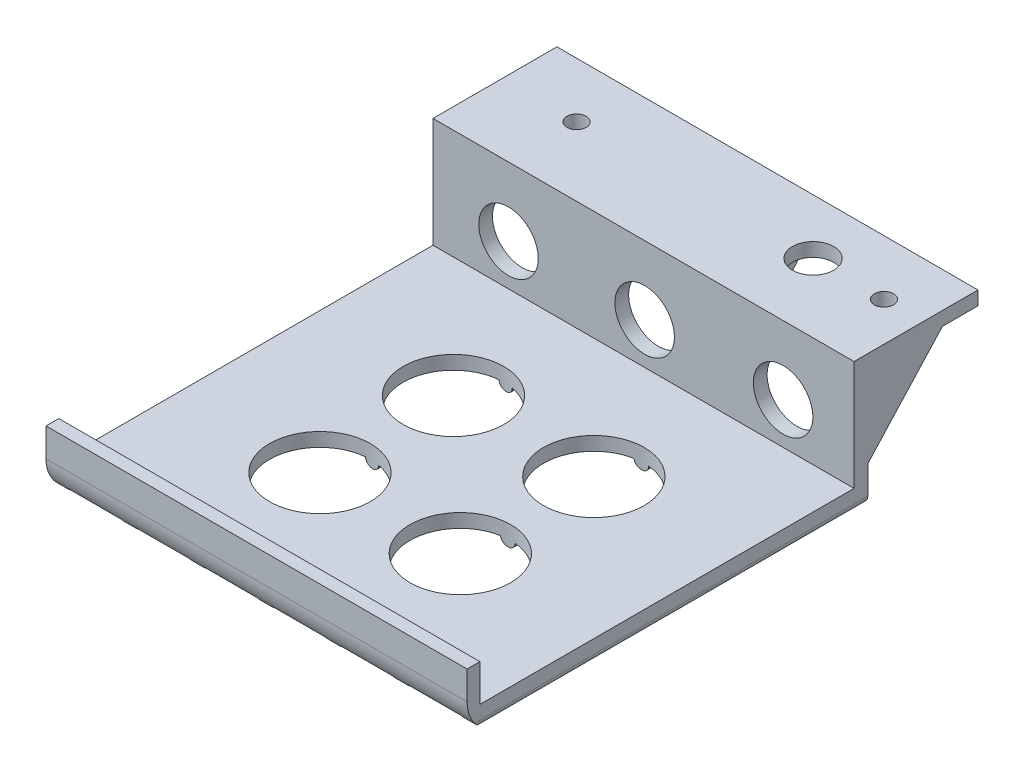
SolidWorks part; units mm, degrees
ref_plane "Plan de face" through (0, 0, 0) normal (0, 0, 1) x (1, 0, 0)
ref_plane "Plan de dessus" through (0, 0, 0) normal (0, 1, 0) x (1, 0, 0)
ref_plane "Plan de droite" through (0, 0, 0) normal (1, 0, 0) x (0, 0, -1)
sketch "Esquisse1" plane through (0, 0, 0) normal (1, 0, 0) x (0, 0, -1)
  line L0 (-109.4897, -87.8002) -> (-136.5699, -87.8002)
  line L1 (-136.5699, -109.8002) -> (-136.5699, -44.8002) construction
  line L2 (-136.5699, -87.8002) -> (-136.5699, -111.8002)
  line L3 (-136.5699, -111.8002) -> (-218.1141, -111.8002)
  line L6 (-109.4897, -90.8002) -> (-133.5699, -90.8002)
  line L7 (-133.5699, -90.8002) -> (-133.5699, -114.8002)
  line L8 (-133.5699, -114.8002) -> (-221.1141, -114.8002)
  line L9 (-221.1141, -114.8002) -> (-221.1141, -103.7104)
  line L10 (-109.4897, -87.8002) -> (-109.4897, -90.8002)
  line L11 (-112.5699, -87.8002) -> (-136.5699, -87.8002) construction
  line L12 (-112.5699, -90.8002) -> (-133.5699, -90.8002) construction
  line L13 (-218.3141, -103.7104) -> (-221.1141, -103.7104)
  line L14 (-218.3141, -103.7104) -> (-218.3141, -111.8002)
  line L15 (-218.1141, -111.8002) -> (-218.3141, -111.8002)
  line L17 (-218.1141, -111.8002) -> (-218.1141, -103.7104) construction
  dimension "D2" = 0.2
  dimension "D1" = 3
extrude "Boss.-Extru.1" add sketch "Esquisse1" against normal blind 92
sketch "Esquisse3" plane through (0, 0, 0) normal (1, 0, 0) x (0, 0, -1)
  line L0 (-117.2572, -90.8002) -> (-133.5699, -108.6357)
  line L1 (-133.5699, -90.8002) -> (-109.4897, -90.8002) construction
  line L2 (-133.5699, -114.8002) -> (-133.5699, -90.8002) construction
rib "Nervure2" sketch "Esquisse3" sketch "Esquisse3" thickness 1 extrusion direction parallel to sketch draft on no parameters "D1"=1
pattern_linear "Répétition linéaire1" count 4 spacing 30 along (-1, 0, 0) of "Nervure2"
sketch "Esquisse4" plane through (0, 0, 133.5699) normal (0, 0, -1) x (-1, 0, 0)
  line L0 (15.5, -90.8002) -> (15.5, -114.8002) construction
  line L1 (30, -90.8002) -> (1, -90.8002) construction
  line L2 (92, -114.8002) -> (0, -114.8002) construction
  line L3 (15.5, -114.8002) -> (46, -114.8002) construction
  line L4 (46, -114.8002) -> (45.5, -90.8002) construction
  line L5 (60, -90.8002) -> (31, -90.8002) construction
  line L6 (45.5, -90.8002) -> (75.5, -90.8002) construction
  line L7 (90, -90.8002) -> (61, -90.8002) construction
  line L8 (75.5, -90.8002) -> (75.5, -114.8002) construction
  circle A0 centre (15.5, -102.8002) radius 6.5
  circle A1 centre (45.75, -102.8002) radius 6.5
  circle A2 centre (75.5, -102.8002) radius 6.5
  dimension "D1" = 13
extrude "Enlèv. mat.-Extru.1" cut sketch "Esquisse4" against normal blind 3
sketch "Esquisse6" plane through (0, 0, 133.5699) normal (0, 0, -1) x (-1, 0, 0)
  line L0 (92, -114.8002) -> (0, -114.8002) construction
  circle A0 centre (1.5, -114.8002) radius 1.5
  point P5 (1.3243, -114.8002)
  dimension "D1" = 3
extrude "Boss.-Extru.2" add sketch "Esquisse6" against normal up to surface (87.5442 mm away) up to face at (-46, -109.2553, 221.1141)
pattern_linear "Répétition linéaire2" count 7 spacing 14.8333 along (-1, 0, 0) of "Boss.-Extru.2"
sketch "Esquisse5" plane through (0, -114.8002, 0) normal (0, -1, 0) x (-1, 0, 0)
  line L0 (0, -162.7513) -> (30.6667, -162.7513) construction
  line L1 (0, -221.1141) -> (0, -133.5699) construction
  line L2 (30.6667, -162.7513) -> (61.3333, -162.7513) construction
  line L3 (61.3333, -162.7513) -> (92, -162.7513) construction
  line L4 (92, -221.1141) -> (92, -133.5699) construction
  line L5 (30.6667, -133.5699) -> (30.6667, -162.7513) construction
  line L6 (92, -133.5699) -> (0, -133.5699) construction
  line L7 (30.6667, -162.7513) -> (30.6667, -191.9327) construction
  line L8 (30.6667, -191.9327) -> (30.6667, -221.1141) construction
  line L9 (92, -221.1141) -> (0, -221.1141) construction
  line L10 (30.6667, -191.9327) -> (61.3333, -191.9327) construction
  circle A0 centre (30.6667, -162.7513) radius 11
  circle A1 centre (61.3333, -162.7513) radius 11
  circle A2 centre (61.3333, -191.9327) radius 11
  circle A3 centre (30.6667, -191.9327) radius 11
  dimension "D1" = 22
extrude "Enlèv. mat.-Extru.2" cut sketch "Esquisse5" against normal blind 3 and the other way blind 3
sketch "Esquisse7" plane through (0, 0, 0) normal (1, 0, 0) x (0, 0, -1)
  line L0 (-221.1141, -113.2428) -> (-218.0568, -116.3002)
  line L1 (-221.1141, -103.7104) -> (-221.1141, -114.8002) construction
  line L2 (-221.1141, -116.3002) -> (-133.5699, -116.3002) construction
  line L3 (-221.1141, -113.2428) -> (-221.1141, -116.3002)
  line L4 (-221.1141, -114.8002) -> (-221.1141, -116.3002) construction
  line L5 (-221.1141, -116.3002) -> (-218.0568, -116.3002)
  dimension "D1" = 45
  dimension "D2" = 3
extrude "Enlèv. mat.-Extru.3" cut sketch "Esquisse7" against normal up to surface (92 mm away) up to face at (-92, -101.7822, 163.8116)
fillet "Congé1" radius 8 1 edges at (-46, -113.2428, 221.1141)
sketch "Esquisse9" plane through (0, -90.8002, 0) normal (0, -1, 0) x (1, 0, 0)
  line L0 (-92, 121.5298) -> (-24, 121.5298) construction
  line L1 (-92, 133.5699) -> (-92, 109.4897) construction
  circle A0 centre (-24, 121.5298) radius 4.5
  dimension "D2" = 9
  dimension "D1" = 68
extrude "Enlèv. mat.-Extru.5" cut sketch "Esquisse9" against normal blind 3
sketch "Esquisse8" plane through (0, -90.8002, 0) normal (0, -1, 0) x (1, 0, 0)
  line L0 (-8.5065, 133.5699) -> (-8.5065, 109.4897) construction
  line L2 (-92, 109.4897) -> (0, 109.4897) construction
  line L3 (-8.5065, 109.4897) -> (-75.6667, 109.4897) construction
  line L4 (-75.6667, 109.4897) -> (-75.6667, 133.5699) construction
  line L5 (-77.1667, 133.5699) -> (-74.1667, 133.5699) construction
  line L7 (-14.8333, 133.5699) -> (-3, 133.5699) construction
  circle A0 centre (-8.5065, 121.5298) radius 2.1
  circle A1 centre (-75.6667, 121.5298) radius 2.1
  point P2 (0, 0)
  point P14 (0, 0)
  point P16 (0, 0)
  dimension "D1" = 4.2
extrude "Enlèv. mat.-Extru.4" cut sketch "Esquisse8" against normal blind 3
